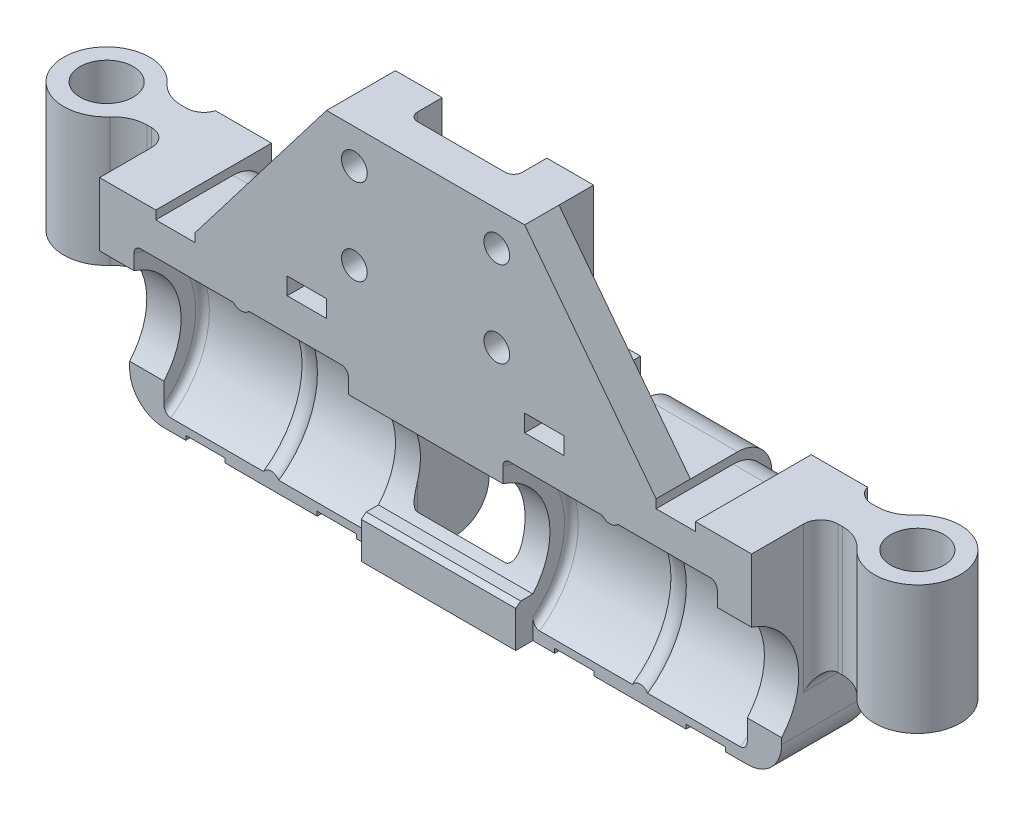
SolidWorks part; units mm, degrees
note: '?' marks a value the reader was unsure of.
ref_plane "Front Plane" through (0, 0, 0) normal (0, 0, 1) x (1, 0, 0)
ref_plane "Top Plane" through (0, 0, 0) normal (0, 1, 0) x (1, 0, 0)
ref_plane "Right Plane" through (0, 0, 0) normal (1, 0, 0) x (0, 0, -1)
sketch "Sketch1" plane through (0, 0, 0) normal (0, 0, 1) x (1, 0, 0)
  line L2 (0, 0) -> (0, 19.9169) construction
  line L3 (0, 0) -> (69.2216, 0) construction
  circle A0 centre (0, 0) radius 9 construction
sketch "Sketch2" plane through (0, 0, 0) normal (0, 0, 1) x (1, 0, 0)
  line L0 (22.3944, 10.5) -> (33.2, 10.5)
  line L2 (20.6056, 10.5) -> (9.8, 10.5)
  line L3 (9, 0) -> (9, 9.7)
  line L5 (9, 0) -> (34, 0)
  line L6 (34, 0) -> (34, 9.7)
  arc A0 (20.6056, 10.5) -> (22.3944, 10.5) centre (21.5, 11.3) ccw
  arc A2 (9.8, 10.5) -> (9, 9.7) centre (9.8, 9.7) ccw
  arc A3 (33.2, 10.5) -> (34, 9.7) centre (33.2, 9.7) cw
  dimension "D1" = 25
sketch "Sketch3" plane through (0, 0, 0) normal (0, 0, 1) x (1, 0, 0)
  line L0 (21.5, 18.5) -> (0, 18.5) construction
  line L1 (0, 0) -> (0, 19.9169) construction
  circle A0 centre (21.5, 15) radius 2
  circle A1 centre (21.5, 15) radius 3.5 construction
sketch "Sketch4" plane through (0, 0, 0) normal (0, 0, 1) x (1, 0, 0)
  line L0 (21.5, 20) -> (21.5, 15) construction
  line L1 (11.5497, 15) -> (0, 15)
  line L2 (31.4503, 15) -> (38, 15)
  line L4 (2.5, 15) -> (40.5, 15) construction
  line L5 (16.1323, 15) -> (26.8677, 15)
  line L6 (11.5497, 14) -> (16.1323, 14)
  line L7 (0, 15) -> (0, 25)
  line L8 (0, 0) -> (0, 19.9169) construction
  line L9 (38, 15) -> (38, 25)
  line L10 (0, 25) -> (38, 25)
  line L12 (31.4503, 14) -> (26.8677, 14)
  line L13 (11.5497, 14) -> (11.5497, 15)
  line L14 (16.1323, 14) -> (16.1323, 15)
  line L15 (26.8677, 14) -> (26.8677, 15)
  line L16 (31.4503, 14) -> (31.4503, 15)
  line L17 (0, 0) -> (-49.4401, 0) construction
  circle A0 centre (21.5, 15) radius 2 construction
  circle A2 centre (21.5, 15) radius 3.5 construction
sketch "Sketch5" plane through (0, 0, 0) normal (1, 0, 0) x (0, 0, -1)
  line L1 (2.5, 18.5) -> (16, 18.5)
  line L2 (2.5, 18.5) -> (2.5, 7.5993)
  line L3 (6, -5.2915) -> (6, -10)
  line L4 (6, -10) -> (16, -10)
  line L5 (16, -10) -> (16, 18.5)
  circle A0 centre (0, 0) radius 10.5 construction
  arc A2 (2.5, 7.5993) -> (6, -5.2915) centre (0, 0) cw
extrude "Boss-Extrude1" add sketch "Sketch5" along normal blind 38 separate body
revolve "Cut-Revolve1" cut sketch "Sketch2" angle 360 about L3
sketch "Sketch7" plane through (0, -10, 0) normal (0, -1, 0) x (1, 0, 0)
  line L3 (0, -6) -> (38, -6) construction
  line L4 (21.5, 0) -> (21.5, -18.5) construction
ref_plane "Plane1" through (0, 0, -6) normal (0, 0, 1) x (1, 0, 0)
ref_axis "Axis2" through (120.2323, 0, 0) along (-1, 0, 0)?
sketch "Sketch11" plane through (0, 0, 0) normal (0, 0, 1) x (1, 0, 0)
  line L0 (21.5, 15) -> (21.5, -10) construction
  line L1 (31.4503, -9.5) -> (26.8677, -9.5)
  line L2 (26.8677, -10.5) -> (31.4503, -10.5)
  line L3 (13.841, -15) -> (13.841, -10) construction
  line L4 (2.5, -10) -> (40.5, -10) construction
  line L5 (11.5497, -10.5) -> (11.5497, -9.5)
  line L6 (16.1323, -9.5) -> (16.1323, -10.5)
  line L7 (16.1323, -10.5) -> (11.5497, -10.5)
  line L8 (11.5497, -9.5) -> (16.1323, -9.5)
  line L9 (29.159, -15) -> (29.159, -10) construction
  line L11 (26.8677, -9.5) -> (26.8677, -10.5)
  line L12 (31.4503, -10.5) -> (31.4503, -9.5)
  line L17 (0, 0) -> (-49.4401, 0) construction
sketch "Sketch12" plane through (0, 0, 0) normal (1, 0, 0) x (0, 0, -1)
  line L0 (0, 0) -> (0, -11.6619) construction
  line L4 (0, 9) -> (0, -9) construction
  circle A0 centre (0, 0) radius 11.6619 construction
extrude "Cut-Extrude1" cut sketch "Sketch4" against normal blind 38
extrude "Cut-Extrude2" cut sketch "Sketch11" against normal blind 30
ref_plane "Plane2" through (0, -10, 0) normal (0, -1, 0) x (1, 0, 0)
sketch "Sketch13" plane through (0, -10, 0) normal (0, -1, 0) x (1, 0, 0)
  line L0 (21.5, 15) -> (21.5, -10) construction
  line L1 (31.4503, -15.5) -> (26.8677, -15.5)
  line L2 (26.8677, -16.5) -> (31.4503, -16.5)
  line L3 (13.841, -21) -> (13.841, -16) construction
  line L4 (2.5, -16) -> (40.5, -16) construction
  line L5 (11.5497, -16.5) -> (11.5497, -15.5)
  line L6 (16.1323, -15.5) -> (16.1323, -16.5)
  line L7 (16.1323, -16.5) -> (11.5497, -16.5)
  line L8 (11.5497, -15.5) -> (16.1323, -15.5)
  line L9 (29.159, -21) -> (29.159, -16) construction
  line L10 (13.841, -17.5) -> (13.841, -16) construction
  line L11 (26.8677, -15.5) -> (26.8677, -16.5)
  line L12 (31.4503, -16.5) -> (31.4503, -15.5)
  line L13 (16.1323, -16) -> (11.5497, -16) construction
  line L17 (0, 0) -> (-49.4401, 0) construction
extrude "Cut-Extrude3" cut sketch "Sketch13" against normal blind 30
fillet "Fillet1" radius 4 4 edges at (13.841, -9.5, -15.5) (29.159, -9.5, -15.5) (13.841, 14, -15.5) (29.159, 14, -15.5)
mirror "Mirror1" about plane through (0, 0, 0) normal (1, 0, 0) of bodies 111
ref_plane "Plane3" through (0, -10, 0) normal (0, -1, 0) x (1, 0, 0)
sketch "Sketch14" plane through (0, -10, 0) normal (0, -1, 0) x (1, 0, 0)
  line L0 (0, 0) -> (0, 23.2641) construction
  line L1 (6.1, -17.6718) -> (6.1, -7.6718)
  line L2 (-5.1, -6.6718) -> (5.1, -6.6718)
  line L4 (-5.1, -18.6718) -> (5.1, -18.6718)
  line L5 (-6.1, -17.6718) -> (-6.1, -7.6718)
  arc A0 (-5.1, -18.6718) -> (-6.1, -17.6718) centre (-5.1, -17.6718) cw
  arc A1 (5.1, -18.6718) -> (6.1, -17.6718) centre (5.1, -17.6718) ccw
  arc A2 (6.1, -7.6718) -> (5.1, -6.6718) centre (5.1, -7.6718) ccw
  arc A3 (-6.1, -7.6718) -> (-5.1, -6.6718) centre (-5.1, -7.6718) cw
  dimension "D1" = 1
  dimension "D2" = 1
extrude "Cut-Extrude4" cut sketch "Sketch14" against normal blind 40
combine bodies "Combine1" operation type add bodies to combine 115 114
sketch "Sketch15" plane through (0, 15, 0) normal (0, 1, 0) x (-1, 0, 0)
  line L0 (-6.1, -8.662) -> (-6.1, -10.5345)
  line L4 (-11.5497, -10.5345) -> (-11.5497, -2.5)
  line L5 (11.5497, -2.5) -> (11.5497, -10.5345)
  line L6 (-6.1, -8.662) -> (-6.1, -7.6718)
  line L7 (11.5497, -16) -> (11.5497, -2.5) construction
  line L8 (-6.1, -16) -> (-6.1, -7.6718) construction
  line L9 (5.1, -6.6718) -> (-5.1, -6.6718)
  line L10 (-6.1, -10.5345) -> (-11.5497, -10.5345)
  line L11 (11.5497, -2.5) -> (-11.5497, -2.5)
  line L12 (11.5497, -10.5345) -> (6.1, -10.5345)
  line L13 (6.1, -7.6718) -> (6.1, -16) construction
  line L14 (6.1, -10.5345) -> (6.1, -7.6718)
  arc A0 (6.1, -7.6718) -> (5.1, -6.6718) centre (5.1, -7.6718) ccw
  arc A1 (-6.1, -7.6718) -> (-5.1, -6.6718) centre (-5.1, -7.6718) cw
  dimension "D1" = 1
extrude "Boss-Extrude2" add sketch "Sketch15" along normal blind 20
sketch "Sketch18" plane through (0, 0, -2.5) normal (0, 0, 1) x (1, 0, 0)
  line L0 (-16.1323, 15) -> (-16.1323, 16)
  line L1 (-16.1323, 16) -> (-11.5497, 16)
  line L3 (-16.1323, 15) -> (-26.8677, 15)
  line L4 (-26.8677, 15) -> (-11.5497, 35)
  line L5 (-11.5497, 35) -> (-11.5497, 16)
  line L6 (0, 0) -> (0, 46.106) construction
  line L7 (11.5497, 35) -> (11.5497, 16)
  line L8 (26.8677, 15) -> (11.5497, 35)
  line L9 (16.1323, 15) -> (26.8677, 15)
  line L10 (16.1323, 16) -> (11.5497, 16)
  line L11 (16.1323, 15) -> (16.1323, 16)
extrude "Boss-Extrude4" add sketch "Sketch18" against normal blind 4
fillet "Fillet3" radius 4 9 edges at (34.7252, -10, -16) (21.5, -10, -16) (-8.8248, -10, -16) (-34.7252, -10, -16) (-21.5, -10, -16) (-21.5, 15, -16) (21.5, 15, -16) (38, -10, -11) (-38, -10, -11)
sketch "Sketch19" plane through (0, 0, -6) normal (0, 0, 1) x (1, 0, 0)
  line L1 (0, -10) -> (38, -10) construction
  line L2 (-9, -5.2915) -> (9, -5.2915)
  line L3 (-9, -5.2915) -> (-9, -10)
  line L4 (-9, -10) -> (9, -10)
  line L5 (9, -5.2915) -> (9, -10)
extrude "Boss-Extrude5" add sketch "Sketch19" along normal blind 2
sketch "Sketch20" plane through (0, 0, 0) normal (1, 0, 0) x (0, 0, -1)
  circle A0 centre (0, 0) radius 7
extrude "Cut-Extrude5" cut sketch "Sketch20" against normal mid plane 22
ref_plane "Plane4" through (0, 0, 0) normal (0, -1, 0) x (1, 0, 0)
sketch "Sketch22" plane through (0, 0, 0) normal (0, -1, 0) x (1, 0, 0)
  line L0 (0, 0) -> (0, -22.6296) construction
  line L2 (38, -14.5718) -> (38, -10.5718)
  line L4 (40.5418, -10.5718) -> (38, -10.5718)
  line L5 (40.5418, -14.5718) -> (38, -14.5718)
  line L6 (-40.5418, -14.5718) -> (-38, -14.5718)
  line L7 (-40.5418, -10.5718) -> (-38, -10.5718)
  line L8 (-38, -14.5718) -> (-38, -10.5718)
  circle A0 centre (47.25, -12.5718) radius 3.1
  arc A1 (-40.5418, -10.5718) -> (-43.5232, -9.2385) centre (-40.5418, -6.5718) cw
  arc A2 (43.5232, -9.2385) -> (43.5232, -15.9051) centre (47.25, -12.5718) cw
  arc A3 (-40.5418, -14.5718) -> (-43.5232, -15.9051) centre (-40.5418, -18.5718) ccw
  arc A4 (40.5418, -14.5718) -> (43.5232, -15.9051) centre (40.5418, -18.5718) cw
  arc A5 (40.5418, -10.5718) -> (43.5232, -9.2385) centre (40.5418, -6.5718) ccw
  arc A6 (-43.5232, -9.2385) -> (-43.5232, -15.9051) centre (-47.25, -12.5718) ccw
  circle A7 centre (-47.25, -12.5718) radius 3.1
  dimension "D1" = 4
extrude "Boss-Extrude6" add sketch "Sketch22" against normal blind 15
fillet "Fillet4" radius 2 6 edges at (-38, 7.5, -10.5718) (-38, 7.5, -14.5718) (38, 7.5, -10.5718) (38, 7.5, -14.5718) (38, 0, -12.5718) (-38, 0, -12.5718)
sketch "Sketch23" plane through (0, 0, -2.5) normal (0, 0, 1) x (1, 0, 0)
  line L0 (0, 0) -> (0, 27.7386) construction
  line L4 (0, -11.6619) -> (0, 11.6619) construction
  circle A0 centre (8.3, 21) radius 1.5
  circle A1 centre (-8.3, 31) radius 1.5
  circle A2 centre (8.3, 31) radius 1.5
  circle A3 centre (-8.3, 21) radius 1.5
extrude "Cut-Extrude6" cut sketch "Sketch23" against normal blind 10
